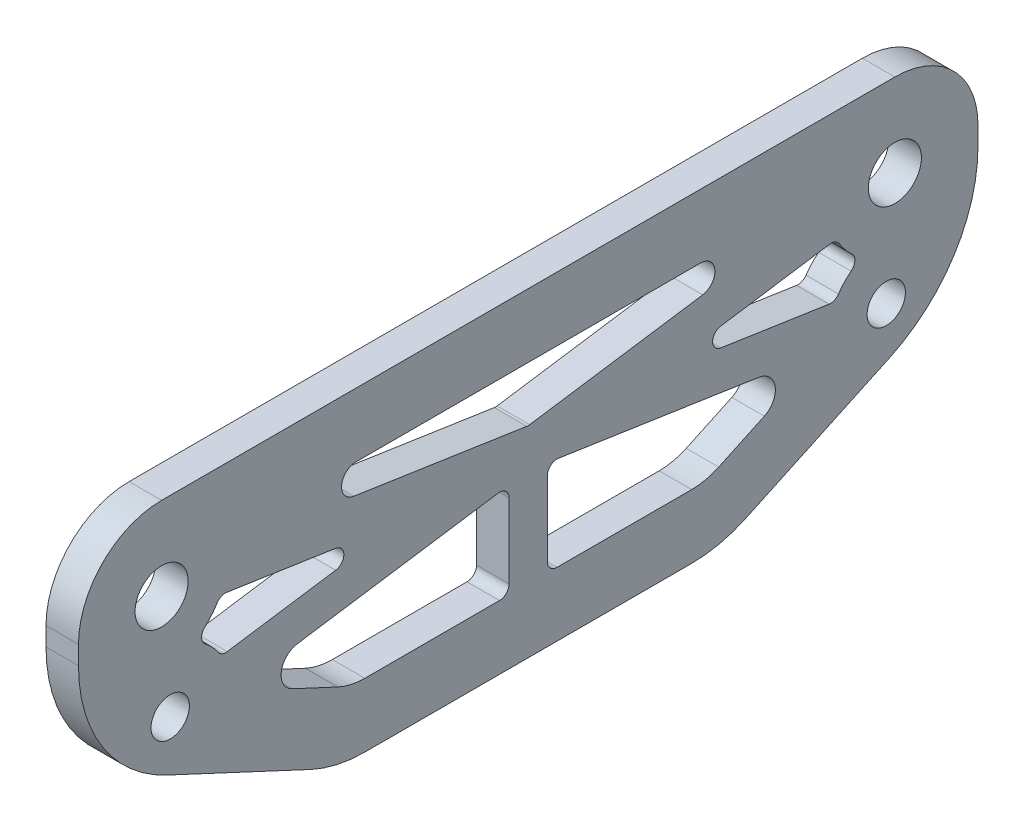
SolidWorks part; units mm, degrees
ref_plane "Front Plane" through (0, 0, 0) normal (0, 0, 1) x (1, 0, 0)
ref_plane "Top Plane" through (0, 0, 0) normal (0, 1, 0) x (1, 0, 0)
ref_plane "Right Plane" through (0, 0, 0) normal (1, 0, 0) x (0, 0, -1)
sketch "Sketch1" plane through (0, 0, 0) normal (1, 0, 0) x (0, 0, -1)
  line L0 (15, 12.5) -> (28.675, 12.5)
  line L1 (-15, -12.5) -> (15, -12.5)
  line L3 (-15, 12.5) -> (15, 12.5)
  line L5 (-15, -12.5) -> (15, 12.5) construction
  line L6 (-15, 12.5) -> (15, -12.5) construction
  line L8 (0, 12.5) -> (0, -12.5) construction
  line L10 (-15, 12.5) -> (-28.675, 12.5)
  line L11 (23.175, 185.452) -> (23.175, -41.948) construction
  line L13 (35.175, 6) -> (35.175, 4.5526)
  line L14 (28.2464, -6.3231) -> (15, -12.5)
  line L16 (-35.175, 6) -> (-35.175, 4.5526)
  line L17 (-28.2464, -6.3231) -> (-15, -12.5)
  arc A0 (28.675, 12.5) -> (35.175, 6) centre (28.675, 6) cw
  circle A1 centre (28.675, 6) radius 5.5 construction
  circle A2 centre (-28.675, 6) radius 5.5 construction
  arc A3 (-28.675, 12.5) -> (-35.175, 6) centre (-28.675, 6) ccw
  arc A4 (35.175, 4.5526) -> (28.2464, -6.3231) centre (23.175, 4.5526) cw
  circle A5 centre (28.675, 6) radius 2.075
  arc A6 (-35.175, 4.5526) -> (-28.2464, -6.3231) centre (-23.175, 4.5526) ccw
  circle A9 centre (-28.675, 6) radius 2.075
  circle A11 centre (28, -2.5) radius 1.5
  circle A12 centre (-28, -2.5) radius 1.5
  point P0 (0, 0)
  point P28 (0, 0)
  dimension "D1" = 11
  dimension "D2" = 1
  dimension "D3" = 4.15
  dimension "D4" = 3
  dimension "D6" = 25
  dimension "D8" = 12
  dimension "D5" = 25
  dimension "D7" = 30
  dimension "D9" = 28
  dimension "D10" = 2.5
extrude "Boss-Extrude1" add sketch "Sketch1" along normal blind 2.54
fillet "Fillet1" radius 10 2 edges at (1.27, -12.5, -15) (1.27, -12.5, 15)
sketch "Sketch2" plane through (0, 0, 0) normal (1, 0, 0) x (0, 0, -1)
  line L0 (-28.675, 6) -> (28, -2.5) construction
  line L10 (-28.675, -2.6012) -> (28.675, 6)
  line L11 (-28.675, 6) -> (28, -2.5)
  line L12 (-28.8975, 4.5166) -> (27.7775, -3.9834)
  line L13 (-28.4525, 7.4834) -> (28.2225, -1.0166)
  line L14 (-28.8975, 4.5166) -> (-28.4525, 7.4834)
  line L15 (27.7775, -3.9834) -> (28.2225, -1.0166)
  line L16 (-12.7831, -7.5) -> (12.7831, -7.5)
  line L17 (14.8961, -7.0315) -> (26.1333, -1.7916)
  line L18 (30.175, 4.5526) -> (30.175, 6)
  line L19 (28.675, 7.5) -> (-28.675, 7.5)
  line L20 (-30.175, 6) -> (-30.175, 4.5526)
  line L21 (-26.1333, -1.7916) -> (-14.8961, -7.0315)
  line L22 (-12.7831, -7.5) -> (12.7831, -7.5)
  line L23 (14.8961, -7.0315) -> (26.1333, -1.7916)
  line L24 (30.175, 4.5526) -> (30.175, 6)
  line L25 (28.675, 7.5) -> (-28.675, 7.5)
  line L26 (-30.175, 6) -> (-30.175, 4.5526)
  line L27 (-26.1333, -1.7916) -> (-14.8961, -7.0315)
  line L28 (-28.4525, -4.0846) -> (28.8975, 4.5166)
  line L29 (-28.8975, -1.1178) -> (28.4525, 7.4834)
  line L30 (-28.4525, -4.0846) -> (-28.8975, -1.1178)
  line L31 (28.8975, 4.5166) -> (28.4525, 7.4834)
  line L32 (0, -7.5) -> (0, 7.5) construction
  line L33 (0, 1.6994) -> (0, -7.5)
  line L34 (-1.5, 1.6994) -> (-1.5, -7.5)
  line L35 (1.5, 1.6994) -> (1.5, -7.5)
  line L36 (-1.5, 1.6994) -> (1.5, 1.6994)
  line L37 (-1.5, -7.5) -> (1.5, -7.5)
  arc A0 (-18.0527, -2.5249) -> (-18.4641, -5.3678) centre (-17.8302, -4.0083) ccw
  arc A1 (18.0527, -2.5249) -> (18.4641, -5.3678) centre (17.8302, -4.0083) cw
  circle A2 centre (-28, -2.5) radius 4.5
  circle A3 centre (-28, -2.5) radius 4.5
  circle A5 centre (28, -2.5) radius 4.5
  circle A6 centre (28, -2.5) radius 4.5
  circle A11 centre (-28.675, 6) radius 5.075
  arc A12 (12.7831, -7.5) -> (14.8961, -7.0315) centre (12.7831, -2.5) ccw
  arc A13 (26.1333, -1.7916) -> (30.175, 4.5526) centre (23.175, 4.5526) ccw
  arc A14 (30.175, 6) -> (28.675, 7.5) centre (28.675, 6) ccw
  arc A15 (-28.675, 7.5) -> (-30.175, 6) centre (-28.675, 6) ccw
  arc A16 (-30.175, 4.5526) -> (-26.1333, -1.7916) centre (-23.175, 4.5526) ccw
  arc A17 (-14.8961, -7.0315) -> (-12.7831, -7.5) centre (-12.7831, -2.5) ccw
  arc A18 (12.7831, -7.5) -> (14.8961, -7.0315) centre (12.7831, -2.5) ccw
  arc A19 (26.1333, -1.7916) -> (30.175, 4.5526) centre (23.175, 4.5526) ccw
  arc A20 (30.175, 6) -> (28.675, 7.5) centre (28.675, 6) ccw
  arc A21 (-28.675, 7.5) -> (-30.175, 6) centre (-28.675, 6) ccw
  arc A22 (-30.175, 4.5526) -> (-26.1333, -1.7916) centre (-23.175, 4.5526) ccw
  arc A23 (-14.8961, -7.0315) -> (-12.7831, -7.5) centre (-12.7831, -2.5) ccw
  circle A24 centre (-28.675, 6) radius 5.075
  circle A26 centre (28.675, 6) radius 5.075
  circle A27 centre (28.675, 6) radius 5.075
  arc A32 (13.477, 7.5) -> (13.6439, 5.2624) centre (13.477, 6.375) cw
  arc A33 (-13.477, 7.5) -> (-13.6439, 5.2624) centre (-13.477, 6.375) ccw
  dimension "D11" = 3
  dimension "D12" = 1.125
  dimension "D2" = 1.5
  dimension "D1" = 5
  dimension "D3" = 3
  dimension "D4" = 3
  dimension "D6" = 1.5
  dimension "D7" = 1.5
  dimension "D8" = 1.5
  dimension "D9" = 1.5
  dimension "D13" = 1.5
  dimension "D14" = 1.5
  dimension "D15" = 3
extrude "Cut-Extrude2" cut sketch "Sketch2" along normal through all contours A24 A3 L29 L12 | A27 L28 L13 A6 | L25 A33 L13 L29 A32 | A1 L12 L35 L22 | L28 A0 L22 L34 region at (0, 1.7005, 19.9688) region at (0, -4.2389, 9.1911) region at (0, 5.8357, 0) region at (0, -4.2389, -9.1911) region at (0, 1.7005, -19.9688)
fillet "Fillet2" radius 0.75 13 edges at (1.27, -7.5, -1.5) (1.27, 3.7975, -24.1028) (1.27, 1.6994, -10.1133) (1.27, 3.7975, 24.1028) (1.27, 3.2162, 0) (1.27, -0.0424, -1.5) (1.27, -7.5, 1.5) (1.27, -0.0424, 1.5) (1.27, 1.6994, 10.1133) (1.27, -0.3873, -24.0268) (1.27, 1.6002, -26.1457) (1.27, -0.3873, 24.0268) (1.27, 1.6002, 26.1457)
